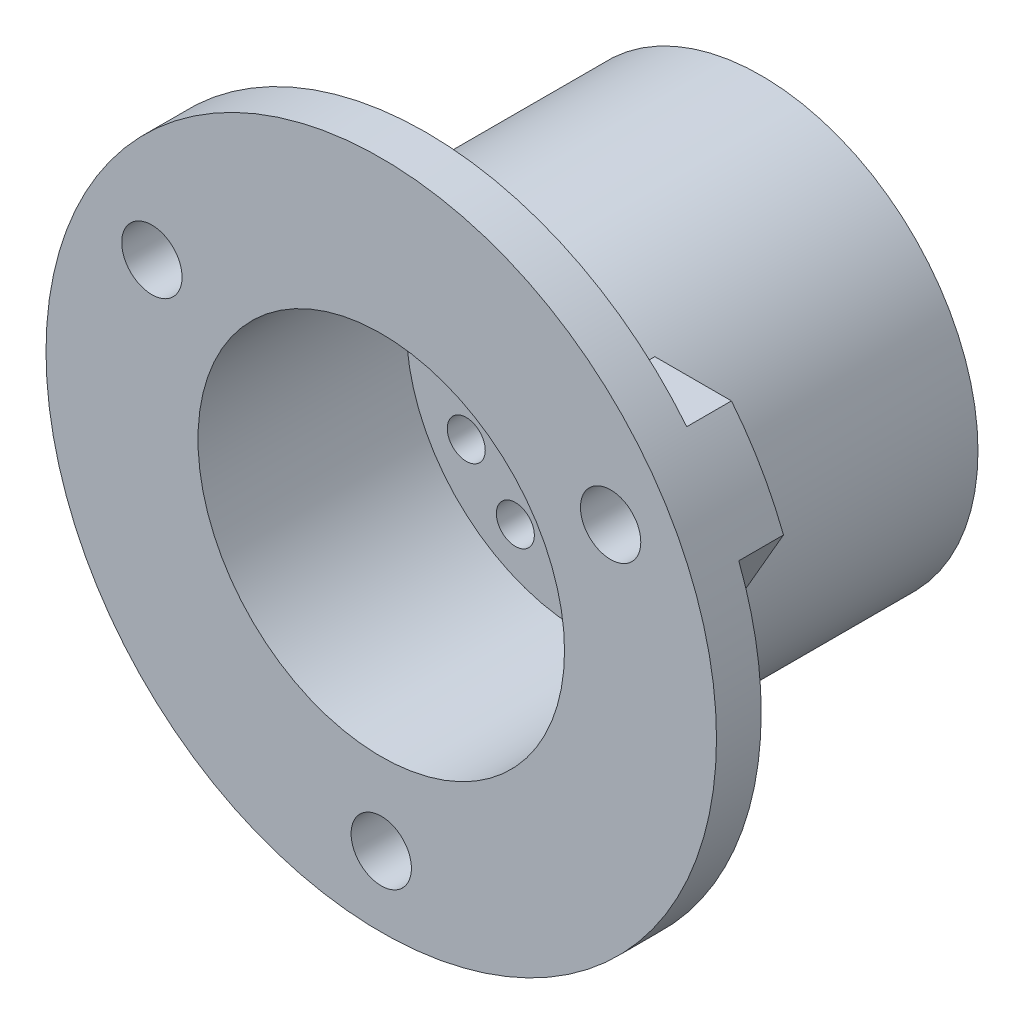
SolidWorks part; units mm, degrees
other "Spi connector"
ref_plane "Front Plane" through (0, 0, 0) normal (0, 0, 1) x (1, 0, 0)
ref_plane "Top Plane" through (0, 0, 0) normal (0, 1, 0) x (1, 0, 0)
ref_plane "Right Plane" through (0, 0, 0) normal (1, 0, 0) x (0, 0, -1)
sketch "Sketch1" plane through (0, 0, 0) normal (0, 0, 1) x (1, 0, 0)
  line L2 (1.75, -2.4) -> (-1.75, -2.4) construction
  circle A0 centre (0, 0) radius 7.875
  circle A1 centre (0, 6) radius 0.85
  circle A2 centre (3, 5.1962) radius 0.85
  circle A3 centre (5.1962, 3) radius 0.85
  circle A4 centre (6, 0) radius 0.85
  circle A5 centre (5.1962, -3) radius 0.85
  circle A6 centre (3, -5.1962) radius 0.85
  circle A7 centre (0, -6) radius 0.85 [skipped]
  circle A8 centre (-3, -5.1962) radius 0.85
  circle A9 centre (-5.1962, -3) radius 0.85
  circle A10 centre (-6, 0) radius 0.85
  circle A11 centre (-5.1962, 3) radius 0.85
  circle A12 centre (-3, 5.1962) radius 0.85
  circle A13 centre (1.75, -2.4) radius 0.85
  circle A14 centre (-1.75, -2.4) radius 0.85
  circle A15 centre (0, 1.6) radius 1.25
  point P30 (0, 0)
  point P34 (0, -2.4)
  dimension "D1" = 15.75
  dimension "D2" = 1.7
  dimension "D7" = 2.5
  dimension "D3" = 6
  dimension "D5" = 2.4
  dimension "D6" = 3.5
  dimension "D8" = 1.6
  dimension "D4" = 12
extrude "Boss-Extrude1" add sketch "Sketch1" along normal blind 5
sketch "Sketch2" plane through (0, 0, 0) normal (0, 0, 1) x (1, 0, 0)
  line L0 (0, -7.2) -> (0, -9.2) construction
  line L1 (1.5, -7.2) -> (1.5, -9.2)
  line L2 (-1.5, -7.2) -> (-1.5, -9.2)
  circle A0 centre (0, 0) radius 8.2
  arc A1 (1.5, -7.2) -> (-1.5, -7.2) centre (0, -7.2) ccw
  arc A2 (-1.5, -9.2) -> (1.5, -9.2) centre (0, -9.2) ccw
  circle A3 centre (0, 0) radius 12
  point P5 (0, -8.2)
  dimension "D1" = 16.4
  dimension "D2" = 1.5
  dimension "D4" = 24
  dimension "D3" = 1
sketch "Sketch3" [suppressed] plane through (0, 0, 0) normal (0, 0, 1) x (1, 0, 0)
  line L0 (-1.5, -7.2) -> (-1.5, -9.2) construction
  line L1 (-1.5, -8.0616) -> (-1.5, -9.2)
  line L2 (1.5, -7.2) -> (1.5, -9.2) construction
  line L3 (1.5, -8.0616) -> (1.5, -9.2)
  circle A0 centre (0, 0) radius 8.2 construction
  arc A1 (1.5, -8.0616) -> (-1.5, -8.0616) centre (0, 0) ccw
  arc A2 (-1.5, -9.2) -> (1.5, -9.2) centre (0, -9.2) ccw construction
  arc A3 (-1.5, -9.2) -> (1.5, -9.2) centre (0, -9.2) ccw
extrude "Extrude-Thin1" add sketch "Sketch2" along normal blind 14 and the other way blind 3 separate body thin contours A0 thin type one direction wall 1.5
sketch "Sketch4" plane through (0, 0, 14) normal (0, 0, 1) x (1, 0, 0)
  line L1 (2.3094, -11.85) -> (1.1547, -9.85)
  line L2 (1.1547, -9.85) -> (-1.1547, -9.85)
  line L3 (-1.1547, -9.85) -> (-2.3094, -11.85)
  line L4 (-2.3094, -11.85) -> (-1.1547, -13.85)
  line L5 (-1.1547, -13.85) -> (1.1547, -13.85)
  line L6 (1.1547, -13.85) -> (2.3094, -11.85)
  line L7 (4.0415, -11.85) -> (2.0207, -8.35)
  line L8 (2.0207, -8.35) -> (-2.0207, -8.35)
  line L9 (-2.0207, -8.35) -> (-4.0415, -11.85)
  line L10 (-4.0415, -11.85) -> (-2.0207, -15.35)
  line L11 (-2.0207, -15.35) -> (2.0207, -15.35)
  line L12 (2.0207, -15.35) -> (4.0415, -11.85)
  circle A0 centre (0, 0) radius 9.7 construction
  circle A1 centre (0, 0) radius 9.7
  circle A2 centre (0, 0) radius 15
  circle A3 centre (0, -11.85) radius 1.35
  circle A5 centre (0, -11.85) radius 2 construction
  circle A6 centre (0, -11.85) radius 3.5 construction
  circle A7 centre (-10.2624, 5.925) radius 1.35
  circle A8 centre (10.2624, 5.925) radius 1.35
  point P6 (9.6774, -0.6623)
  point P21 (0, 0)
  point P26 (0, 0)
  point P27 (0.3268, -9.6945)
  point P28 (0.9232, -10.4872)
  point P29 (0, -12.0023)
  circle M1 centre (0, 0) radius 9.7
  dimension "D1" = 30
  dimension "D2" = 2.7
  dimension "D3" = 4
  dimension "D5" = 0.15
  dimension "D4" = 1.5
  dimension "D6" = 3
extrude "Boss-Extrude2" add sketch "Sketch4" against normal blind 2 contours A2 | A1 | A3
extrude "Boss-Extrude3" add sketch "Sketch4<4>" against normal blind 2 from surface contours L7 A2 L9 L10 L12 L6 L5 L4 L3 L2 L1 M1 region at (3.0992, -13.2848, 14) starting at face at (1.35, -11.85, 12)
sketch "Sketch4<4>" plane through (0, 0, 14) normal (0, 0, 1) x (1, 0, 0) same geometry as "Sketch4"
pattern_circular "CirPattern1" count 3 over 360 about axis through (0, 0, -3) along (0, 0, 1) of "Boss-Extrude3", "Boss-Extrude2"
extrude "Cut-Extrude1" cut sketch "Sketch4<5>" against normal blind 2 contours A7 | A8 | A3 region at (0, -11.85, 14) region at (-10.2624, 5.925, 14) region at (10.2624, 5.925, 14)
sketch "Sketch4<5>" plane through (0, 0, 14) normal (0, 0, 1) x (1, 0, 0) same geometry as "Sketch4"
